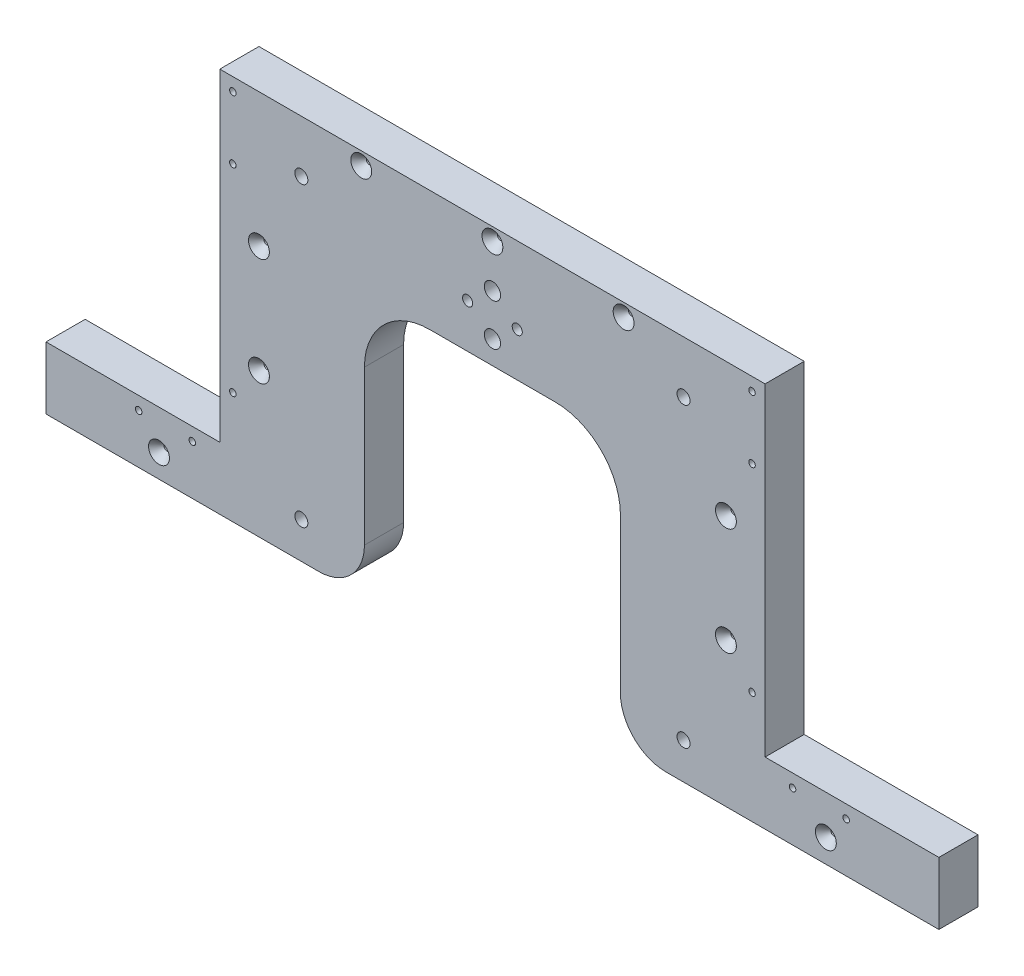
SolidWorks part; units mm, degrees
material "Beech"
ref_plane "Front Plane" through (0, 0, 0) normal (0, 0, 1) x (1, 0, 0)
ref_plane "Top Plane" through (0, 0, 0) normal (0, 1, 0) x (1, 0, 0)
ref_plane "Right Plane" through (0, 0, 0) normal (1, 0, 0) x (0, 0, -1)
sketch "Sketch1" plane through (0, 0, 0) normal (0, 0, 1) x (1, 0, 0)
  line L0 (-341.3045, -157.3) -> (-341.3045, -175)
  line L1 (-124.0045, 12.7) -> (-124.0045, -46)
  line L2 (-341.3045, -157.3) -> (-341.3045, -144.6)
  line L3 (-341.3045, -144.6) -> (-244.0045, -144.6)
  line L6 (-244.0045, -144.6) -> (-244.0045, 12.7)
  line L7 (-244.0045, 12.7) -> (-124.0045, 12.7)
  line L8 (-4.0045, 12.7) -> (-244.0045, 12.7) construction
  line L13 (-124.0045, -46) -> (-186.3045, -46)
  line L14 (-186.3045, -46) -> (-186.3045, -175)
  line L15 (-186.3045, -175) -> (-341.3045, -175)
  dimension "D2" = 17.7
  dimension "D1" = 12.7
  dimension "D6" = 58.7
  dimension "D7" = 155
extrude "Boss-Extrude2" add sketch "Sketch1" along normal blind 19.05 contours L13 L14 L15 L0 L2 L3 L6 L7 L1
fillet "Fillet1" radius 22.225 1 edges at (-186.3045, -175, 9.525)
fillet "Fillet2" radius 31.75 1 edges at (-186.3045, -46, 9.525)
sketch "Sketch6" plane through (-244.0045, 0, 0) normal (-1, 0, 0) x (0, 0, 1)
  line L4 (0, 12.7) -> (0, -144.6)
  line L5 (0, -144.6) -> (19.05, -144.6)
  line L6 (19.05, -144.6) -> (19.05, 12.7)
  line L7 (19.05, 12.7) -> (0, 12.7)
  line L8 (0, 12.7) -> (0, -144.6)
  line L9 (0, -144.6) -> (19.05, -144.6)
  line L10 (19.05, -144.6) -> (19.05, 12.7)
  line L11 (19.05, 12.7) -> (0, 12.7)
  dimension "D1" = 0
extrude "Boss-Extrude3" add sketch "Sketch6" along normal up to surface (12.7 mm away)
mirror "Mirror1" about plane through (-124.0045, 12.7, 19.05) normal (1, 0, 0) of "Fillet2", "Fillet1", "Boss-Extrude2", "Boss-Extrude3"
hole_wizard "5/16 (0.3125) Diameter Hole1" positions "Sketch2" profile "Sketch3" hole size "5/16" standard "ANSI Inch" end condition through all
sketch "Sketch2" plane through (0, 0, 0) normal (0, 0, -1) x (-1, 0, 0)
  circle A0 centre (124.0045, -14.4275) radius 3.5712 construction
  circle A1 centre (124.0045, -34.7475) radius 3.5712 construction
  point P0 (124.0045, -34.7475)
  point P2 (124.0045, -14.4275)
sketch "Sketch3" plane through (-124.0045, -34.7475, 0) normal (1, 0, 0) x (0, 1, 0)
  line L0 (0, 0) -> (0, 19.05)
  line L1 (0, 19.05) -> (3.9687, 19.05)
  line L2 (3.9687, 19.05) -> (3.9688, 0)
  line L5 (3.9688, 0) -> (0, 0)
  line L11 (0, -6.35) -> (0, 107.95) construction
  dimension "Thru Hole Dia." = 7.9375
  dimension "Thru Hole Depth" = 19.05
hole_wizard "#8 Clearance Hole1" positions "Sketch4" profile "Sketch5" hole size "#8" standard "ANSI Inch" end condition through all
sketch "Sketch4" plane through (0, 0, 19.05) normal (0, 0, 1) x (1, 0, 0)
  point P0 (-111.9272, -24.5875)
  point P2 (-136.0817, -24.5875)
sketch "Sketch5" plane through (-111.9272, -24.5875, 19.05) normal (1, 0, 0) x (0, -1, 0)
  line L0 (0, 0) -> (0, 19.05)
  line L1 (0, 19.05) -> (2.4574, 19.05)
  line L2 (2.4574, 19.05) -> (2.4574, 0)
  line L5 (2.4574, 0) -> (0, 0)
  line L11 (0, -6.35) -> (0, 107.95) construction
  dimension "Thru Hole Dia." = 4.9149
  dimension "Thru Hole Depth" = 19.05
hole_wizard "Hole1" positions "Sketch7" profile "Sketch8" legacy
sketch "Sketch7" plane through (-124.0045, -66.1243, 19.05) normal (0, 0, 1) x (1, 0, 0)
  point P15 (-162.3, -97.5257)
  point P34 (-113.65, -38.7424)
  point P36 (-113.65, 13.691)
  point P54 (162.3, -97.5257)
  point P55 (113.65, -38.7424)
  point P56 (113.65, 13.691)
  point P71 (63.85, 72.4743)
  point P73 (0, 72.4743)
  point P74 (-63.85, 72.4743)
sketch "Sketch8" plane through (-286.3045, -163.65, 19.05) normal (1, 0, 0) x (0, -1, 0)
  line L0 (0, 0) -> (0, 32.7039)
  line L1 (0, 32.7039) -> (1.5875, 31.75)
  line L2 (1.5875, 31.75) -> (1.5875, 4.0177)
  line L3 (1.5875, 4.0177) -> (5.08, 0)
  line L4 (5.08, 0) -> (0, 0)
  line L5 (0, -14.3089) -> (0, 102.4216) construction
  line L6 (0, 32.7039) -> (-1.5875, 31.75) construction
  line L7 (-1.5875, 4.0177) -> (-5.08, 0) construction
  dimension "Diameter" = 3.175
  dimension "Depth" = 31.75
  dimension "C-Sink Diameter" = 10.16
  dimension "C-Sink Angle" = 82
  dimension "Drill Angle" = 118
hole_wizard "Hole2" positions "Sketch9" profile "Sketch10" legacy
sketch "Sketch9" plane through (-124.0045, -66.1243, 0) normal (0, 0, -1) x (-1, 0, 0)
  line L21 (0, 20.1243) -> (0, 66.1243) construction
  point P37 (126.35, 72.4743)
  point P42 (146.0833, -84.8257)
  point P44 (172.1667, -84.8257)
  point P63 (126.35, -54.3757)
  point P65 (126.35, 42.0243)
  point P76 (-172.1667, -84.8257)
  point P77 (-146.0833, -84.8257)
  point P78 (-126.35, -54.3757)
  point P79 (-126.35, 42.0243)
  point P80 (-126.35, 72.4743)
sketch "Sketch10" plane through (-250.3545, 6.35, 0) normal (1, 0, 0) x (0, 1, 0)
  line L0 (0, 0) -> (0, 32.7039)
  line L1 (0, 32.7039) -> (1.5875, 31.75)
  line L2 (1.5875, 31.75) -> (1.5875, 4.0177)
  line L3 (1.5875, 4.0177) -> (5.08, 0)
  line L4 (5.08, 0) -> (0, 0)
  line L5 (0, -14.3089) -> (0, 102.4216) construction
  line L6 (0, 32.7039) -> (-1.5875, 31.75) construction
  line L7 (-1.5875, 4.0177) -> (-5.08, 0) construction
  dimension "Diameter" = 3.175
  dimension "Depth" = 31.75
  dimension "C-Sink Diameter" = 10.16
  dimension "C-Sink Angle" = 82
  dimension "Drill Angle" = 118
hole_wizard "1/4 (0.25) Diameter Hole1" positions "Sketch11" profile "Sketch12" hole size "1/4" standard "ANSI Inch" end condition through all
sketch "Sketch11" plane through (0, 0, 19.05) normal (0, 0, 1) x (1, 0, 0)
  point P0 (-217.017, -157.3)
  point P2 (-217.017, -12.7)
  point P4 (-30.992, -12.7)
  point P6 (-30.992, -157.3)
sketch "Sketch12" plane through (-217.017, -157.3, 19.05) normal (1, 0, 0) x (0, -1, 0)
  line L0 (0, 0) -> (0, 19.05)
  line L1 (0, 19.05) -> (3.175, 19.05)
  line L2 (3.175, 19.05) -> (3.175, 0)
  line L5 (3.175, 0) -> (0, 0)
  line L11 (0, -6.35) -> (0, 107.95) construction
  dimension "Thru Hole Dia." = 6.35
  dimension "Thru Hole Depth" = 19.05
